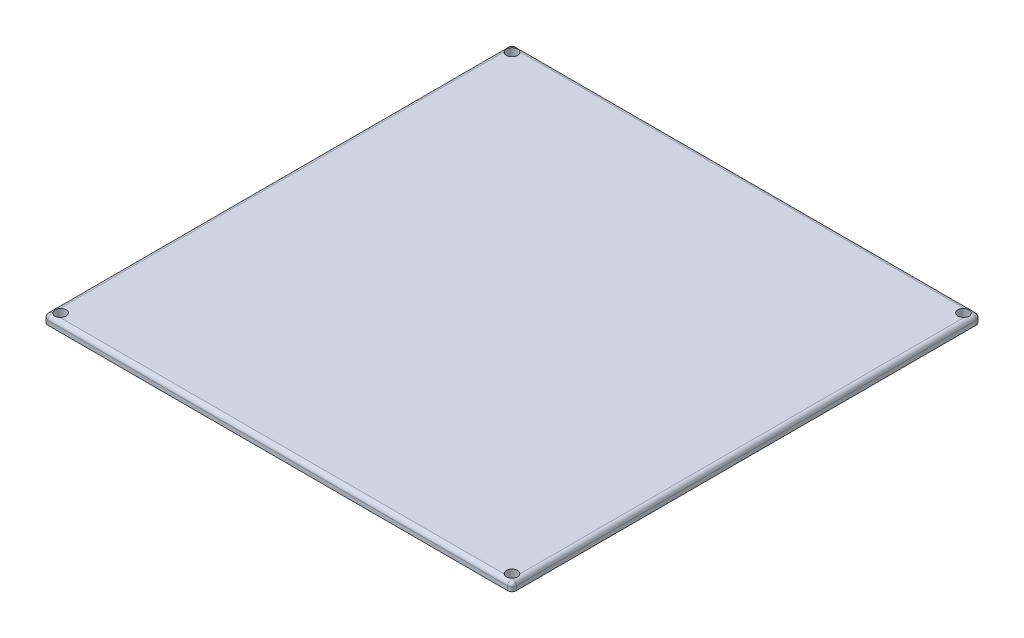
SolidWorks part; units mm, degrees
ref_plane "Plan de face" through (0, 0, 0) normal (0, 0, 1) x (1, 0, 0)
ref_plane "Plan de dessus" through (0, 0, 0) normal (0, 1, 0) x (1, 0, 0)
ref_plane "Plan de droite" through (0, 0, 0) normal (1, 0, 0) x (0, 0, -1)
sketch "Esquisse1" plane through (0, 0, 0) normal (0, 1, 0) x (1, 0, 0)
  line L1 (-58.4375, 35.2344) -> (51.5625, 35.2344)
  line L2 (-58.4375, 35.2344) -> (-58.4375, -74.7656)
  line L3 (-58.4375, -74.7656) -> (51.5625, -74.7656)
  line L4 (51.5625, 35.2344) -> (51.5625, -74.7656)
  circle A0 centre (-56.4375, 33.2344) radius 1.3
  circle A1 centre (49.5625, 33.2344) radius 1.3
  circle A2 centre (-56.4375, -72.7656) radius 1.3
  circle A3 centre (49.5625, -72.7656) radius 1.3
  dimension "D3" = 2.6
  dimension "D4" = 2.6
  dimension "D5" = 2.6
  dimension "D6" = 2.6
  dimension "D7" = 2
  dimension "D8" = 2
  dimension "D9" = 2
  dimension "D10" = 2
  dimension "D11" = 2
  dimension "D12" = 2
  dimension "D13" = 2
  dimension "D14" = 2
  dimension "D1" = 110
  dimension "D2" = 110
extrude "Boss.-Extru.1" add sketch "Esquisse1" along normal blind 2
fillet "Congé2" radius 1 1 edges at (-58.4375, 1, 74.7656)
fillet "Congé3" radius 1 3 edges at (-58.4375, 1, -35.2344) (51.5625, 1, -35.2344) (51.5625, 1, 74.7656)
fillet "Congé5" radius 1 8 edges at (51.2696, 2, 74.4727) (-3.4375, 2, 74.7656) (-58.1446, 2, 74.4727) (-58.4375, 2, 19.7656) (-58.1446, 2, -34.9415) (-3.4375, 2, -35.2344) (51.2696, 2, -34.9415) (51.5625, 2, 19.7656)
